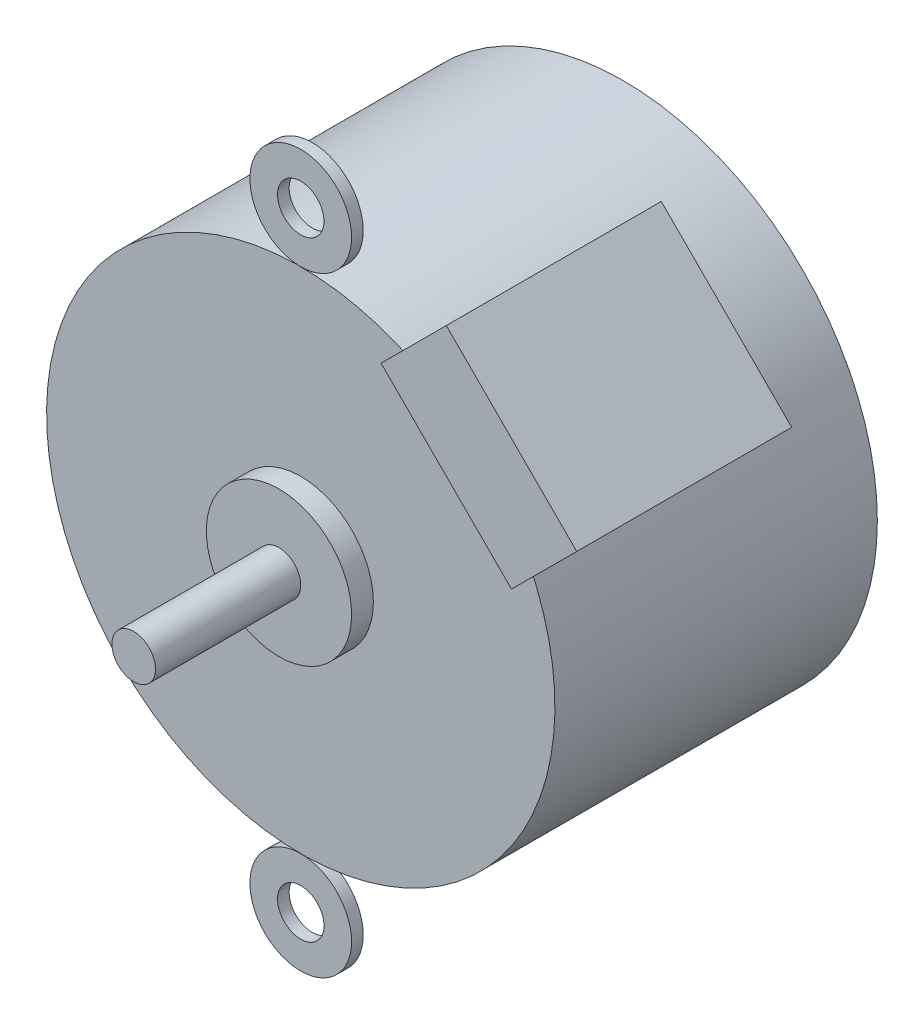
SolidWorks part; units mm, degrees
ref_plane "Front Plane" through (0, 0, 0) normal (0, 0, 1) x (1, 0, 0)
ref_plane "Top Plane" through (0, 0, 0) normal (0, 1, 0) x (1, 0, 0)
ref_plane "Right Plane" through (0, 0, 0) normal (1, 0, 0) x (0, 0, -1)
sketch "Sketch1" plane through (0, 0, 0) normal (0, 0, 1) x (1, 0, 0)
  circle A0 centre (0, 0) radius 17.5
extrude "Boss-Extrude1" add sketch "Sketch1" along normal blind 0.8
sketch "Sketch2" plane through (0, 0, 0) normal (0, 0, 1) x (1, 0, 0)
  circle A0 centre (0, 21) radius 3.5
extrude "Boss-Extrude2" add sketch "Sketch2" along normal blind 0.8
sketch "Sketch3" plane through (0, 0, 0) normal (0, 0, 1) x (1, 0, 0)
  circle A0 centre (0, -21) radius 3.5
extrude "Boss-Extrude3" add sketch "Sketch3" along normal blind 0.8
sketch "Sketch4" plane through (0, 0, 0) normal (0, 0, 1) x (1, 0, 0)
  circle A0 centre (0, 21) radius 1.6
  circle A1 centre (0, -21) radius 1.6
extrude "Cut-Extrude4" cut sketch "Sketch4" along normal blind 1.8
sketch "Sketch5" plane through (0, 0, 0) normal (0, 0, 1) x (1, 0, 0)
  circle A0 centre (0, 0) radius 17.5
extrude "Boss-Extrude4" add sketch "Sketch5" against normal blind 21.4
sketch "Sketch6" plane through (0, 0, 0) normal (0, 0, 1) x (1, 0, 0)
  circle A0 centre (0, 0) radius 4
extrude "Boss-Extrude5" add sketch "Sketch6" against normal blind 22.4
sketch "Sketch7" plane through (0, 0, 0) normal (0, 0, 1) x (1, 0, 0)
  circle A0 centre (0, 0) radius 5
extrude "Boss-Extrude6" add sketch "Sketch7" along normal blind 2.3
sketch "Sketch8" plane through (0, 0, 0) normal (0, 0, 1) x (1, 0, 0)
  circle A0 centre (0, 0) radius 1.5
extrude "Boss-Extrude7" add sketch "Sketch8" along normal blind 12.3
sketch "Sketch9" plane through (0, 0, 0) normal (0, 0, 1) x (1, 0, 0)
  line L0 (16.5109, 7.5307) -> (7.5307, 16.5109)
  line L1 (7.5307, 16.5109) -> (12.0208, 21.0011)
  line L2 (12.0208, 21.0011) -> (21.0011, 12.0208)
  line L3 (21.0011, 12.0208) -> (16.5109, 7.5307)
extrude "Boss-Extrude8" add sketch "Sketch9" against normal blind 12
sketch "Sketch10" plane through (0, 0, 0) normal (0, 0, 1) x (1, 0, 0)
  line L0 (16.5109, 7.5307) -> (7.5307, 16.5109)
  line L1 (7.5307, 16.5109) -> (12.0208, 21.0011)
  line L2 (12.0208, 21.0011) -> (7.5307, 16.5109) construction
  line L3 (12.0208, 21.0011) -> (21.0011, 12.0208)
  line L4 (16.5109, 7.5307) -> (21.0011, 12.0208) construction
  line L5 (21.0011, 12.0208) -> (16.5109, 7.5307)
extrude "Boss-Extrude9" add sketch "Sketch10" along normal blind 2.8
